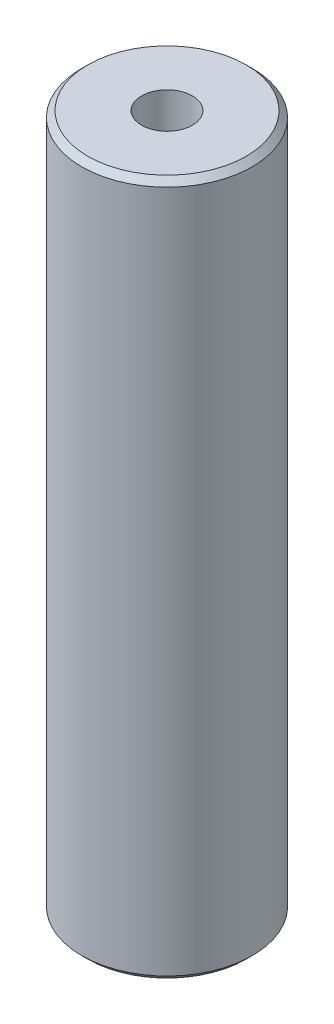
SolidWorks part; units mm, degrees
ref_plane "Front Plane" through (0, 0, 0) normal (0, 0, 1) x (1, 0, 0)
ref_plane "Top Plane" through (0, 0, 0) normal (0, 1, 0) x (1, 0, 0)
ref_plane "Right Plane" through (0, 0, 0) normal (1, 0, 0) x (0, 0, -1)
sketch "Sketch1" plane through (0, 0, 0) normal (0, 1, 0) x (1, 0, 0)
  circle A0 centre (0, 0) radius 50
  dimension "SHAFT_OD" = 100
extrude "Boss-Extrude1" add sketch "Sketch1" along normal blind 407.6297
sketch "Sketch2" plane through (0, 0, 0) normal (0, 1, 0) x (1, 0, 0)
  circle A0 centre (0, 0) radius 14.9053
  dimension "BORE_D" = 29.8106
extrude "Cut-Extrude1" cut sketch "Sketch2" along normal through all
chamfer "Chamfer1" distance 3.5736 angle 45 2 edges at (0, 407.6297, 50) (0, 0, 50)
